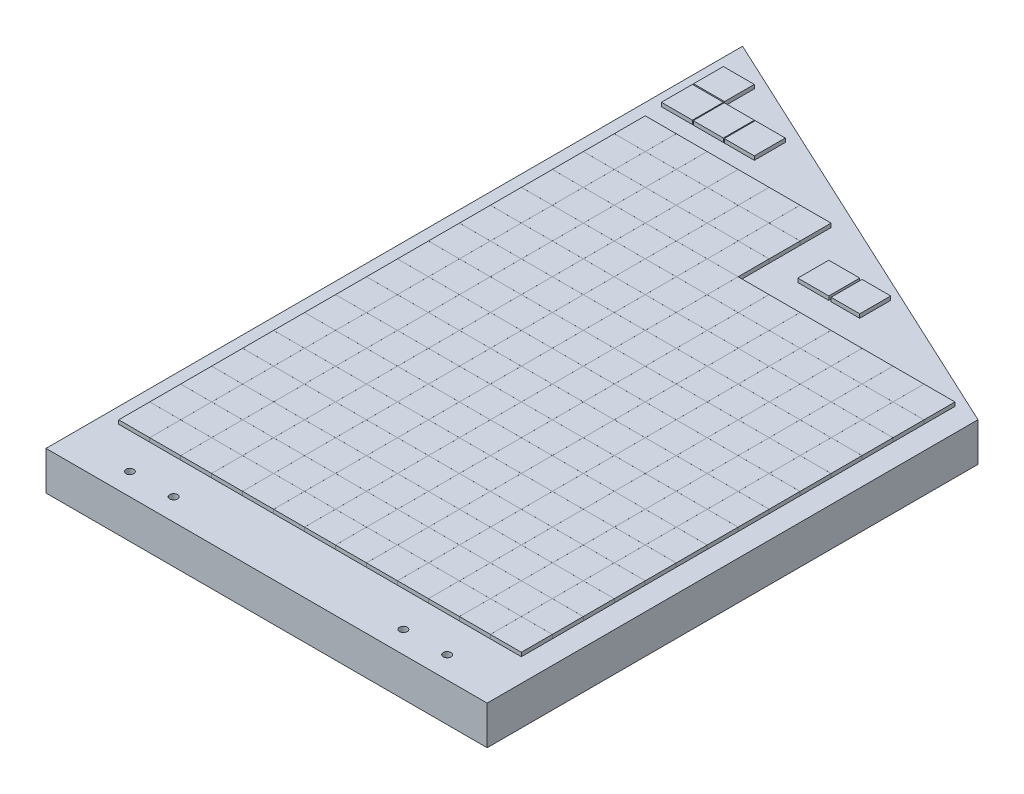
SolidWorks part; units mm, degrees
material "Silicon"
ref_plane "Front Plane" through (0, 0, 0) normal (0, 0, 1) x (1, 0, 0)
ref_plane "Top Plane" through (0, 0, 0) normal (0, 1, 0) x (1, 0, 0)
ref_plane "Right Plane" through (0, 0, 0) normal (1, 0, 0) x (0, 0, -1)
sketch "Sketch1" plane through (0, 0, 0) normal (0, 1, 0) x (1, 0, 0)
  line L0 (-332.5215, 0) -> (391.3785, 0)
  line L1 (-332.5215, 0) -> (-332.5215, 1143)
  line L2 (-332.5215, 1143) -> (391.3785, 805.4399)
  line L3 (391.3785, 805.4399) -> (391.3785, 0)
  dimension "D1" = 723.9
  dimension "D2" = 1143
  dimension "D3" = 65
extrude "Boss-Extrude1" add sketch "Sketch1" along normal blind 63.5
sketch "Sketch2" plane through (0, 63.5, 0) normal (0, 1, 0) x (1, 0, 0)
  line L0 (-332.5215, 1143) -> (-332.5215, 0) construction
  line L1 (-332.5215, 0) -> (391.3785, 0) construction
  line L2 (391.3785, 0) -> (391.3785, 805.4399) construction
  circle A0 centre (-230.9215, 35.941) radius 6.35
  circle A1 centre (-159.0395, 35.941) radius 6.35
  circle A2 centre (217.8965, 35.941) radius 6.35
  circle A3 centre (289.7785, 35.941) radius 6.35
  dimension "D1" = 12.7
  dimension "D2" = 12.7
  dimension "D3" = 12.7
  dimension "D4" = 12.7
  dimension "D5" = 101.6
  dimension "D6" = 71.882
  dimension "D7" = 35.941
  dimension "D8" = 35.941
  dimension "D9" = 101.6
  dimension "D10" = 71.882
  dimension "D11" = 35.941
  dimension "D12" = 35.941
extrude "Cut-Extrude1" cut sketch "Sketch2" against normal through all
sketch "Sketch3" plane through (0, 63.5, 0) normal (0, 1, 0) x (1, 0, 0)
  line L0 (391.3785, 805.4399) -> (-554.0731, 805.4399) construction
  line L1 (-332.5215, 1143) -> (-332.5215, 0) construction
  line L2 (-307.1215, 754.6399) -> (-256.3215, 754.6399)
  line L3 (-307.1215, 754.6399) -> (-307.1215, 805.4399)
  line L4 (-307.1215, 805.4399) -> (-256.3215, 805.4399)
  line L5 (-256.3215, 754.6399) -> (-256.3215, 805.4399)
  dimension "D1" = 50.8
  dimension "D2" = 50.8
  dimension "D3" = 25.4
extrude "Boss-Extrude2" add sketch "Sketch3" along normal blind 6.35
pattern_linear "LPattern1" count 14 spacing 50.8254 along (0, 0, 1) count 13 spacing 50.8254 along (1, 0, 0) of "Boss-Extrude2"
pattern_linear "LPattern2" count 4 spacing 50.8254 along (0, 0, -1) count 6 spacing 50.8254 along (1, 0, 0) of "Boss-Extrude2"
sketch "Sketch6" plane through (0, 63.5, 0) normal (0, 1, 0) x (1, 0, 0)
  line L0 (-313.0913, 1092.0611) -> (-313.0913, 990.4611)
  line L1 (-313.0913, 990.4611) -> (-262.2913, 990.4611)
  line L2 (-262.2913, 990.4611) -> (-262.2913, 1092.0611)
  line L3 (-262.2913, 1092.0611) -> (-313.0913, 1092.0611)
  line L4 (-313.0913, 1041.2611) -> (-160.6913, 1041.2611)
  line L5 (-160.6913, 1041.2611) -> (-160.6913, 990.4611)
  line L6 (-160.6913, 990.4611) -> (-262.2913, 990.4611)
  line L7 (-211.4913, 990.4611) -> (-211.4913, 1041.2611)
  line L8 (-313.0913, 1043.1982) -> (-262.2913, 1043.1982)
  line L9 (-260.8545, 1041.2611) -> (-260.8545, 990.4611)
  line L10 (-209.9806, 1041.2611) -> (-209.9806, 990.4611)
  dimension "D1" = 101.6
  dimension "D2" = 50.8
  dimension "D3" = 50.8
extrude "Boss-Extrude8" add sketch "Sketch6" along normal blind 6.35 contours L0 L4 L2 L3 | L4 L0 L1 L2 | L6 L7 L4 L2 | L7 L6 L5 L4 region at (-287.6913, 63.5, -1067.6296) region at (-287.6913, 63.5, -1015.8611) region at (-236.1729, 63.5, -1015.8611) region at (-185.336, 63.5, -1015.8611)
sketch "Sketch7" plane through (0, 63.5, 0) normal (0, 1, 0) x (1, 0, 0)
  line L0 (48.6309, 903.3322) -> (48.6309, 852.5322)
  line L1 (48.6309, 852.5322) -> (150.2309, 852.5322)
  line L2 (150.2309, 852.5322) -> (150.2309, 903.3322)
  line L3 (150.2309, 903.3322) -> (48.6309, 903.3322)
  line L4 (48.6309, 754.6399) -> (48.6309, 805.4399) construction
  line L5 (99.4309, 852.5322) -> (99.4309, 903.3322)
  line L6 (99.4309, 903.3322) -> (103.2049, 903.3322)
  line L7 (103.2049, 903.3322) -> (103.2049, 852.5322)
  dimension "D1" = 101.6
  dimension "D2" = 50.8
extrude "Boss-Extrude9" add sketch "Sketch7" along normal blind 6.35 contours L1 L5 L3 L0 | L3 L7 L1 L2 region at (74.0309, 63.5, -877.9322) region at (126.7179, 63.5, -877.9322)
